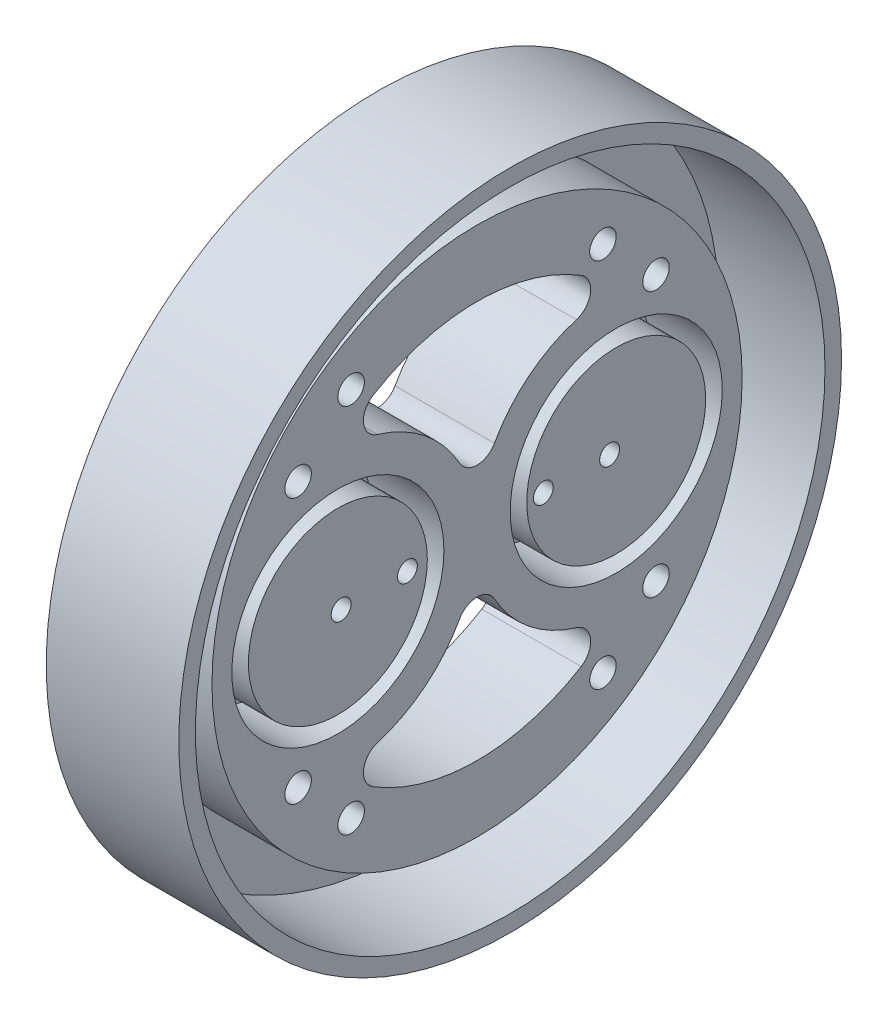
SolidWorks part; units mm, degrees
material "PET"
ref_plane "Front Plane" through (0, 0, 0) normal (0, 0, 1) x (1, 0, 0)
ref_plane "Top Plane" through (0, 0, 0) normal (0, 1, 0) x (1, 0, 0)
ref_plane "Right Plane" through (0, 0, 0) normal (1, 0, 0) x (0, 0, -1)
sketch "Sketch1" plane through (0, 0, 0) normal (1, 0, 0) x (0, 0, -1)
  line L3 (-40, 0) -> (40, 0) construction
  line L4 (0, 40) -> (0, 8.619) construction
  line L5 (0, -8.619) -> (0, -40) construction
  circle A0 centre (0, 0) radius 47.5
  circle A1 centre (0, 0) radius 40
  circle A2 centre (0, 0) radius 50
  circle A3 centre (-21, 0) radius 16
  circle A4 centre (-21, 0) radius 13.5
  circle A5 centre (21, 0) radius 16
  circle A6 centre (21, 0) radius 13.5
  arc A9 (-15, -20.1246) -> (-2.625, -10.1666) centre (-21, 0) ccw
  arc A10 (15, -20.1246) -> (2.625, -10.1666) centre (21, 0) cw
  arc A11 (-15.7143, -25.5551) -> (15.7143, -25.5551) centre (0, 0) ccw
  circle A12 centre (-21, 0) radius 21 construction
  circle A13 centre (0, 0) radius 30 construction
  circle A14 centre (21, 0) radius 21 construction
  arc A15 (15.7143, 25.5551) -> (-15.7143, 25.5551) centre (0, 0) ccw
  arc A16 (2.625, -10.1666) -> (-2.625, -10.1666) centre (0, -11.619) ccw
  arc A17 (-2.625, 10.1666) -> (2.625, 10.1666) centre (0, 11.619) ccw
  arc A18 (-15, -20.1246) -> (-15.7143, -25.5551) centre (-14.1429, -22.9996) ccw
  arc A19 (15, -20.1246) -> (15.7143, -25.5551) centre (14.1429, -22.9996) cw
  arc A20 (15, 20.1246) -> (15.7143, 25.5551) centre (14.1429, 22.9996) ccw
  arc A21 (-15, 20.1246) -> (-15.7143, 25.5551) centre (-14.1429, 22.9996) cw
  arc A22 (-2.625, 10.1666) -> (-15, 20.1246) centre (-21, 0) ccw
  arc A23 (2.625, 10.1666) -> (15, 20.1246) centre (21, 0) cw
  point P35 (21.4286, 20.9956)
  dimension "D1" = 95
  dimension "D2" = 80
  dimension "D3" = 100
  dimension "D4" = 32
  dimension "D5" = 27
  dimension "D7" = 5
  dimension "D9" = 6
  dimension "D10" = 6
  dimension "D11" = 3
  dimension "D6" = 21
  dimension "D8" = 10
extrude "Boss-Extrude1" add sketch "Sketch1" along normal blind 20 contours A2 A0 region at (0, 0, 48.5858)
extrude "Boss-Extrude2" add sketch "Sketch1<3>" along normal blind 4 contours A0 A1 | A1 A3 A5 | A2 A0 | A3 A4 | A4 | A5 A6 | A6 region at (0, 0, 46.1565) region at (0, 0, 0) region at (0, 0, 48.5858) region at (0, 0, 36.5475) region at (0, 0, 21) region at (0, 0, -5.4525) region at (0, 0, -21)
sketch "Sketch1<3>" plane through (0, 0, 0) normal (1, 0, 0) x (0, 0, -1) same geometry as "Sketch1"
extrude "Boss-Extrude3" add sketch "Sketch1<4>" along normal blind 15 contours A1 A3 A5 | A4 | A6 region at (0, 0, 0) region at (0, 0, 21) region at (0, 0, -21)
sketch "Sketch1<4>" plane through (0, 0, 0) normal (1, 0, 0) x (0, 0, -1) same geometry as "Sketch1"
sketch "Sketch2" plane through (15, 0, 0) normal (1, 0, 0) x (0, 0, -1)
  line L2 (0, 0) -> (-59.9166, 0) construction
  line L3 (0, 0) -> (64.9552, 0) construction
  line L4 (0, 0) -> (0, -54.611) construction
  circle A6 centre (-27, -20) radius 2
  circle A7 centre (-19, -28) radius 2
  circle A8 centre (0, 0) radius 50 construction
  circle A10 centre (-20.508, 0) radius 1.5
  circle A11 centre (-10.508, 0) radius 1.5
  circle A12 centre (10, 0) radius 1.5
  circle A13 centre (20, 0) radius 1.5
  circle A14 centre (19, -28) radius 2
  circle A15 centre (27, -20) radius 2
  circle A16 centre (27, 20) radius 2
  circle A17 centre (19, 28) radius 2
  circle A18 centre (-19, 28) radius 2
  circle A19 centre (-27, 20) radius 2
  point P6 (-50, 0)
  dimension "D3" = 8
  dimension "D4" = 4
  dimension "D5" = 4
  dimension "D8" = 3
  dimension "D9" = 3
  dimension "D12" = 3
  dimension "D13" = 3
  dimension "D1" = 20
  dimension "D2" = 8
  dimension "D6" = 29.492
  dimension "D7" = 10
  dimension "D10" = 20.508
  dimension "D11" = 10
  dimension "D14" = 23
extrude "Cut-Extrude1" cut sketch "Sketch2" against normal through all
